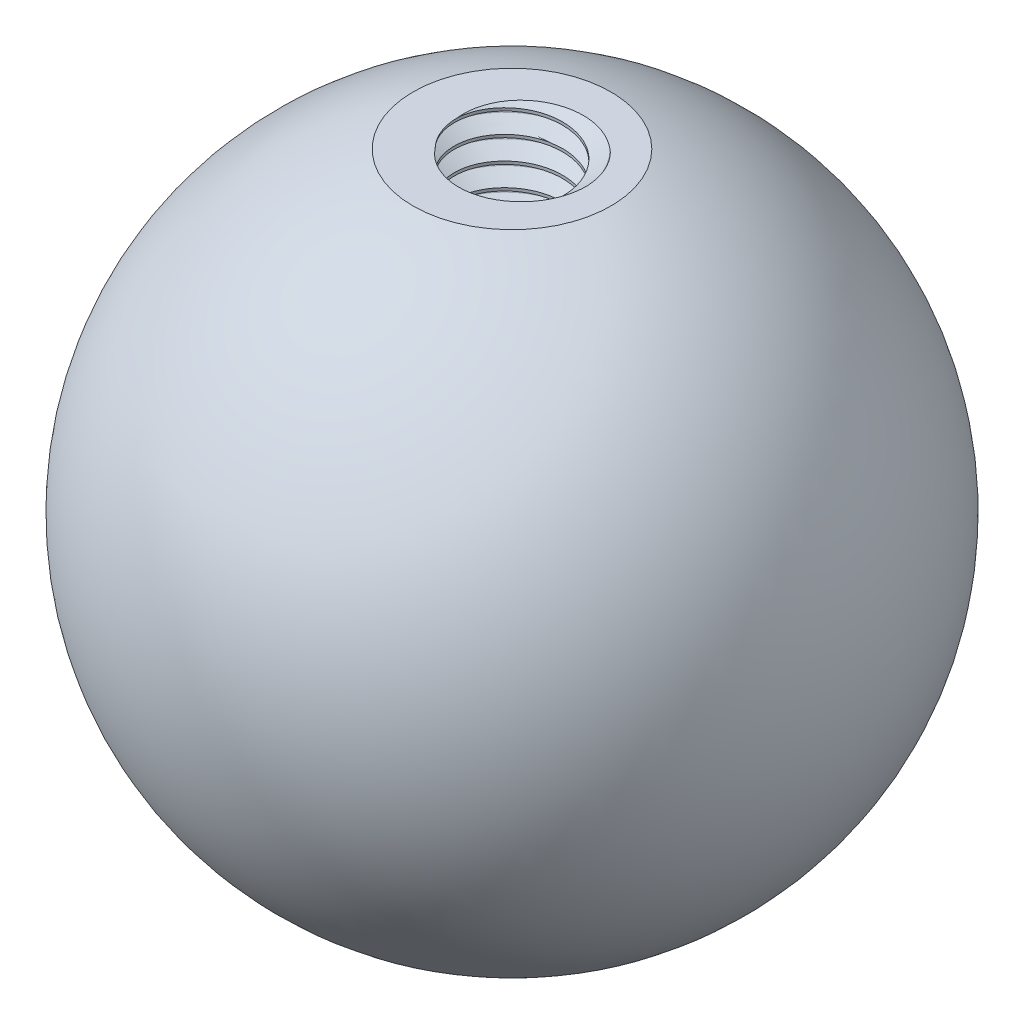
SolidWorks part; units mm, degrees
material "Plástico personalizado"
ref_plane "Alzado" through (0, 0, 0) normal (0, 0, 1) x (1, 0, 0)
ref_plane "Planta" through (0, 0, 0) normal (0, 1, 0) x (1, 0, 0)
ref_plane "Vista lateral" through (0, 0, 0) normal (1, 0, 0) x (0, 0, -1)
sketch "Croquis1" plane through (0, 0, 0) normal (0, 1, 0) x (1, 0, 0)
  circle A0 centre (0, 0) radius 3
extrude "Saliente-Extruir1" add sketch "Croquis1" along normal blind 14
hole_wizard "Perforador para roscar para macho de roscar para M4x0.71" positions "Croquis3D1" profile "Croquis2" hole size "M4x0.7" standard "Ansi Metric"
sketch3d "Croquis3D1"
  line L0 (0, 14, 0) -> (0, 0, 0) construction
  point P0 (0, 14, 0)
sketch "Croquis2" plane through (0, 14, 0) normal (1, 0, 0) x (0, 0, 1)
  line L0 (0, 0) -> (0, 11.9914)
  line L1 (0, 11.9914) -> (1.65, 11)
  line L2 (1.65, 11) -> (1.65, 0)
  line L5 (1.65, 0) -> (0, 0)
  line L10 (0, 11.9914) -> (-1.65, 11) construction
  line L11 (0, -6.35) -> (0, 107.95) construction
  dimension "Diámetro de taladro" = 3.3
  dimension "Profundidad de taladro" = 11
  dimension "Ángulo de perforador" = 118
sketch "Croquis3" plane through (0, 14, 0) normal (0, 1, 0) x (1, 0, 0)
  circle A0 centre (0, 0) radius 1.65 construction
  circle A1 centre (0, 0) radius 1.65
curve "Hélice/Espiral1" pitch 0.7 height 11 turns 15.7143
ref_plane "Plano1" through (-1.65, 14, 0) normal (0, 0, 1) x (1, 0, 0)
sketch "Croquis4" plane through (-1.65, 14, 0) normal (0, 0, 1) x (1, 0, 0)
  line L0 (0, 0) -> (0, 0.6125) construction
  line L1 (0, 0.6125) -> (-0.5304, 0.3062) construction
  line L2 (-0.5304, 0.3062) -> (0, 0) construction
  line L3 (0, 0.3063) -> (-0.5304, 0.3062) construction
  line L4 (-0.5304, 0.3062) -> (-0.5304, 0.8847) construction
  line L5 (-0.4547, 0.3062) -> (-0.4547, 0.8847)
  line L6 (-0.4547, 0.35) -> (0, 0.6125)
  line L7 (0, 0.6125) -> (0, 0)
  line L8 (0, 0) -> (-0.4547, 0.2625)
  arc A0 (-0.4547, 0.35) -> (-0.4547, 0.2625) centre (-0.4294, 0.3062) ccw
  dimension "D1" = 0.6125
  dimension "D2" = 60
  dimension "D3" = 0.0758
sweep "Cortar-Barrer1" cut profiles "Croquis4" path "Hélice/Espiral1"
sketch "Croquis5" plane through (0, 0, 0) normal (0, 0, 1) x (1, 0, 0)
  line L0 (-3, 14) -> (-2.5, 14)
  line L1 (-3, 14) -> (-3, 0) construction
  line L2 (3, 14) -> (-3, 14) construction
  line L3 (-2.5, 14) -> (-2.5, 0.2)
  line L4 (-2.5, 0.2) -> (0, 0.2)
  line L5 (0, 0.2) -> (0, -5.5394)
  arc A0 (-3, 14) -> (0, -5.5394) centre (0, 4.4606) ccw
revolve "Revolución1" add sketch "Croquis5" angle 360 about L5
